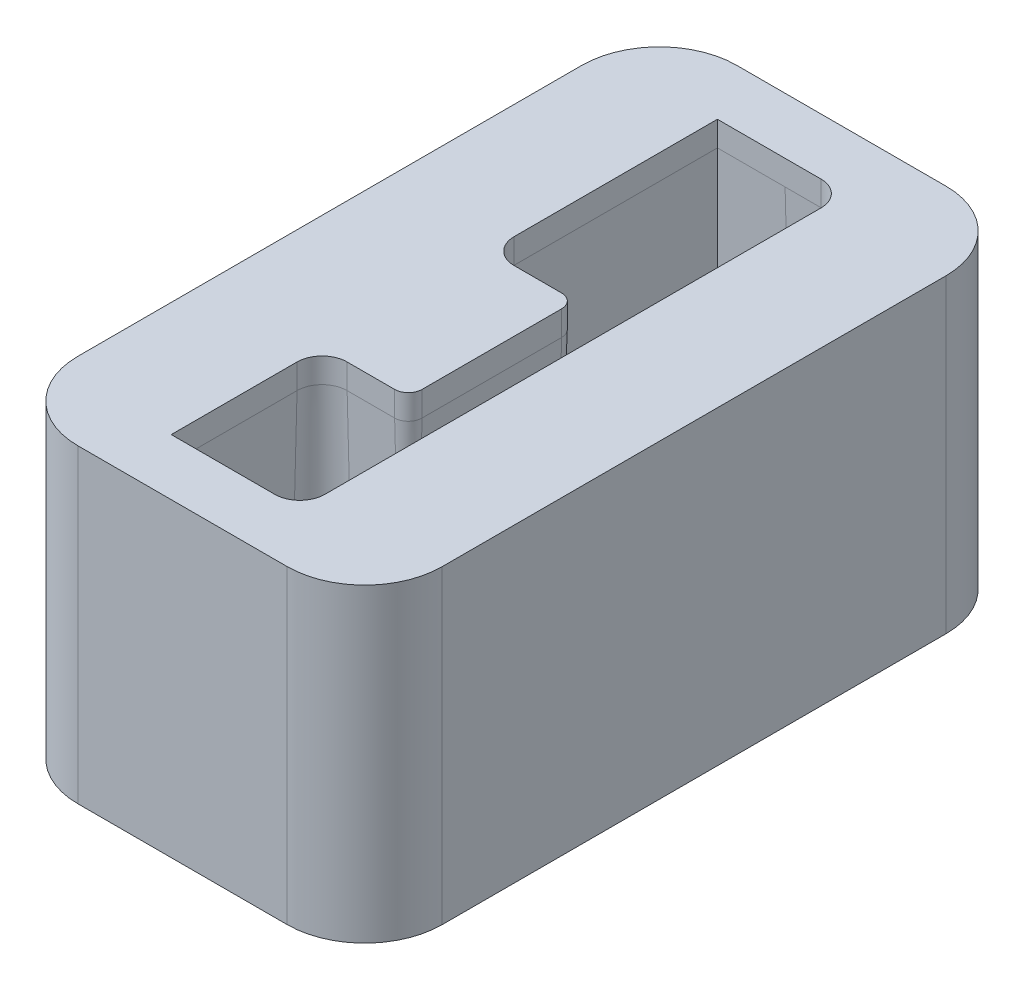
SolidWorks part; units mm, degrees
material "K110"
ref_plane "Front Plane" through (0, 0, 0) normal (0, 0, 1) x (1, 0, 0)
ref_plane "Top Plane" through (0, 0, 0) normal (0, 1, 0) x (1, 0, 0)
ref_plane "Right Plane" through (0, 0, 0) normal (1, 0, 0) x (0, 0, -1)
sketch "Sketch1" plane through (0, 0, 0) normal (0, 1, 0) x (1, 0, 0)
  line L1 (-23.5, -42.5) -> (23.5, -42.5)
  line L2 (-23.5, -42.5) -> (-23.5, 42.5)
  line L3 (-23.5, 42.5) -> (23.5, 42.5)
  line L4 (23.5, -42.5) -> (23.5, 42.5)
  line L5 (-23.5, -42.5) -> (23.5, 42.5) construction
  line L6 (-23.5, 42.5) -> (23.5, -42.5) construction
  point P0 (0, 0)
  dimension "D1" = 85
  dimension "D2" = 47
extrude "Boss-Extrude1" add sketch "Sketch1" against normal blind 40
fillet "Fillet1" radius 10 4 edges at (-23.5, -20, -42.5) (23.5, -20, -42.5) (-23.5, -20, 42.5) (23.5, -20, 42.5)
sketch "Sketch3" plane through (0, 0, 0) normal (0, 1, 0) x (1, 0, 0)
  line L88 (4.63, 35.23) -> (-8.73, 35.23)
  line L89 (-8.73, 35.23) -> (-8.73, 9)
  line L90 (-5.5, 5.77) -> (0.63, 5.77)
  line L91 (2.4, 4) -> (2.4, -14)
  line L92 (0.63, -15.77) -> (-5.5, -15.77)
  line L93 (-8.73, -19) -> (-8.73, -35.23)
  line L94 (-8.73, -35.23) -> (4.63, -35.23)
  line L95 (7.86, -32) -> (7.86, 32)
  line L96 (4.63, 35.23) -> (-8.73, 35.23)
  line L97 (-8.73, 35.23) -> (-8.73, 9)
  line L98 (-5.5, 5.77) -> (0.63, 5.77)
  line L99 (2.4, 4) -> (2.4, -14)
  line L100 (0.63, -15.77) -> (-5.5, -15.77)
  line L101 (-8.73, -19) -> (-8.73, -35.23)
  line L102 (-8.73, -35.23) -> (4.63, -35.23)
  line L103 (7.86, -32) -> (7.86, 32)
  arc A48 (7.86, 32) -> (4.63, 35.23) centre (4.63, 32) ccw
  arc A49 (-8.73, 9) -> (-5.5, 5.77) centre (-5.5, 9) ccw
  arc A50 (2.4, 4) -> (0.63, 5.77) centre (0.63, 4) ccw
  arc A51 (0.63, -15.77) -> (2.4, -14) centre (0.63, -14) ccw
  arc A52 (-5.5, -15.77) -> (-8.73, -19) centre (-5.5, -19) ccw
  arc A53 (4.63, -35.23) -> (7.86, -32) centre (4.63, -32) ccw
  arc A54 (7.86, 32) -> (4.63, 35.23) centre (4.63, 32) ccw
  arc A55 (-8.73, 9) -> (-5.5, 5.77) centre (-5.5, 9) ccw
  arc A56 (2.4, 4) -> (0.63, 5.77) centre (0.63, 4) ccw
  arc A57 (0.63, -15.77) -> (2.4, -14) centre (0.63, -14) ccw
  arc A58 (-5.5, -15.77) -> (-8.73, -19) centre (-5.5, -19) ccw
  arc A59 (4.63, -35.23) -> (7.86, -32) centre (4.63, -32) ccw
  dimension "D1" = 0.23
extrude "Cut-Extrude1" cut sketch "Sketch3" against normal up to next
sketch "Sketch4" plane through (0, 0, 0) normal (1, 0, 0) x (0, 0, -1)
  line L6 (35.23, -3.2) -> (36.1936, -40)
  line L7 (35.23, -40) -> (35.23, 0) construction
  line L9 (36.1936, -40) -> (35.23, -40)
  line L10 (35.23, -40) -> (35.23, -3.2)
  line L11 (25.85, 0) -> (-25.85, 0) construction
  dimension "D1" = 3.2
  dimension "D2" = 1.5
sketch "Sketch5" plane through (0, 0, 0) normal (0, 1, 0) x (1, 0, 0)
  line L16 (-8.73, -35.23) -> (4.63, -35.23) construction
  line L17 (-8.73, -19) -> (-8.73, -35.23) construction
  line L18 (0.63, -15.77) -> (-5.5, -15.77) construction
  line L19 (2.4, 4) -> (2.4, -14) construction
  line L20 (-5.5, 5.77) -> (0.63, 5.77) construction
  line L21 (-8.73, 35.23) -> (-8.73, 9) construction
  line L22 (4.63, 35.23) -> (-8.73, 35.23) construction
  line L23 (7.86, -32) -> (7.86, 32) construction
  line L24 (-8.73, -35.23) -> (4.63, -35.23)
  line L25 (-8.73, -19) -> (-8.73, -35.23)
  line L26 (0.63, -15.77) -> (-5.5, -15.77)
  line L27 (2.4, 4) -> (2.4, -14)
  line L28 (-5.5, 5.77) -> (0.63, 5.77)
  line L29 (-8.73, 35.23) -> (-8.73, 9)
  line L30 (4.63, 35.23) -> (-8.73, 35.23)
  line L31 (7.86, -32) -> (7.86, 32)
  arc A8 (4.63, -35.23) -> (7.86, -32) centre (4.63, -32) ccw construction
  arc A9 (-5.5, -15.77) -> (-8.73, -19) centre (-5.5, -19) ccw construction
  arc A10 (0.63, -15.77) -> (2.4, -14) centre (0.63, -14) ccw construction
  arc A11 (2.4, 4) -> (0.63, 5.77) centre (0.63, 4) ccw construction
  arc A12 (-8.73, 9) -> (-5.5, 5.77) centre (-5.5, 9) ccw construction
  arc A13 (7.86, 32) -> (4.63, 35.23) centre (4.63, 32) ccw construction
  arc A14 (4.63, -35.23) -> (7.86, -32) centre (4.63, -32) ccw
  arc A15 (-5.5, -15.77) -> (-8.73, -19) centre (-5.5, -19) ccw
  arc A16 (0.63, -15.77) -> (2.4, -14) centre (0.63, -14) ccw
  arc A17 (2.4, 4) -> (0.63, 5.77) centre (0.63, 4) ccw
  arc A18 (-8.73, 9) -> (-5.5, 5.77) centre (-5.5, 9) ccw
  arc A19 (7.86, 32) -> (4.63, 35.23) centre (4.63, 32) ccw
sweep "Cut-Sweep1" cut profiles "Sketch4" path "Sketch5"
hole_wizard "M6 Tapped Hole1" positions "Sketch8" profile "Sketch7" tap size "M6" standard "ISO"
sketch "Sketch8" plane through (0, -40, 0) normal (0, -1, 0) x (-1, 0, 0)
  line L0 (-13.5, 42.5) -> (13.5, 42.5) construction
  line L1 (-23.5, -32.5) -> (-23.5, 32.5) construction
  line L2 (23.5, 32.5) -> (23.5, -32.5) construction
  line L3 (13.5, -42.5) -> (-13.5, -42.5) construction
  point P0 (-16.5, 35.5)
  point P2 (16.5, 35.5)
  point P4 (16.5, -35.5)
  point P6 (-16.5, -35.5)
  dimension "D1" = 7
  dimension "D2" = 7
  dimension "D3" = 7
  dimension "D4" = 7
sketch "Sketch7" plane through (16.5, -40, -35.5) normal (1, 0, 0) x (0, 0, -1)
  line L0 (0, 0) -> (0, 18.5022)
  line L1 (0, 18.5022) -> (2.5, 17)
  line L2 (2.5, 17) -> (2.5, 0.525)
  line L3 (2.5, 0.525) -> (3.025, 0)
  line L5 (3.025, 0) -> (0, 0)
  line L6 (-2.5, 0.525) -> (-3.025, 0) construction
  line L10 (0, 18.5022) -> (-2.5, 17) construction
  line L11 (0, -6.35) -> (0, 107.95) construction
  dimension "Tap Drill Dia." = 5
  dimension "Tap Drill Depth" = 17
  dimension "Near C'Sink Dia." = 6.05
  dimension "Near C'Sink Angle" = 90
  dimension "Drill Angle" = 118
cosmetic thread "Hole Thread1"
cosmetic thread "Hole Thread2"
cosmetic thread "Hole Thread3"
cosmetic thread "Hole Thread4"
